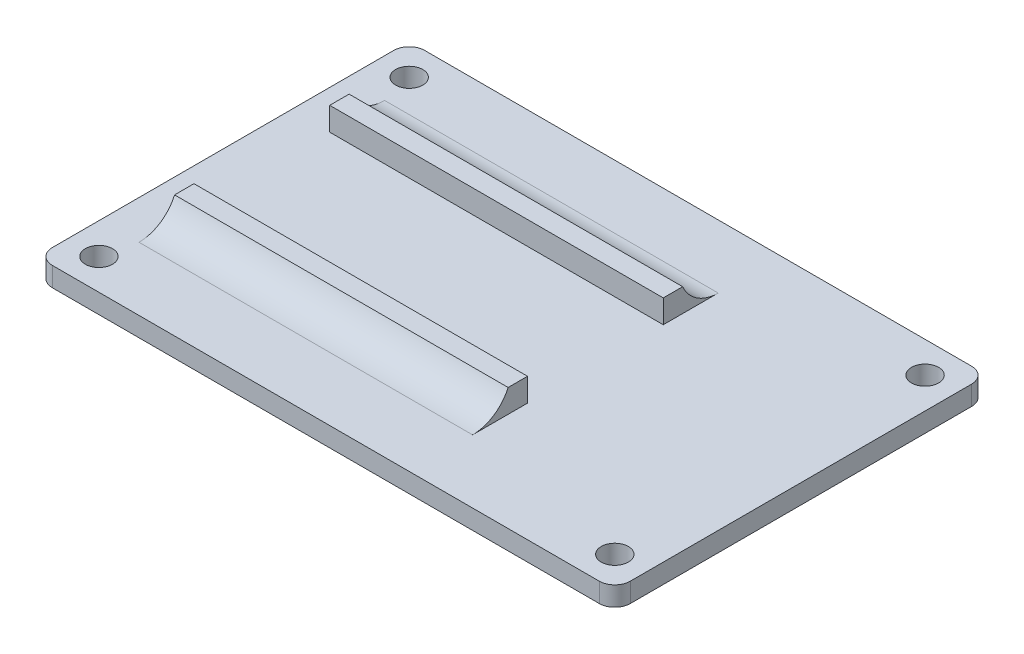
SolidWorks part; units mm, degrees
ref_plane "Front Plane" through (0, 0, 0) normal (0, 0, 1) x (1, 0, 0)
ref_plane "Top Plane" through (0, 0, 0) normal (0, 1, 0) x (1, 0, 0)
ref_plane "Right Plane" through (0, 0, 0) normal (1, 0, 0) x (0, 0, -1)
sketch "Sketch1" plane through (0, 0, 0) normal (0, 1, 0) x (1, 0, 0)
  line L2 (-52.4763, 21.334) -> (18.0237, 21.334)
  line L3 (20.0237, 19.334) -> (20.0237, -24.666)
  line L4 (18.0237, -26.666) -> (-52.4763, -26.666)
  line L5 (-54.4763, -24.666) -> (-54.4763, 19.334)
  circle A0 centre (-50.4763, 17.334) radius 1.75
  circle A1 centre (16.0237, 17.334) radius 1.75
  circle A2 centre (16.0237, -22.666) radius 1.75
  circle A3 centre (-50.4763, -22.666) radius 1.75
  arc A4 (-52.4763, -26.666) -> (-54.4763, -24.666) centre (-52.4763, -24.666) cw
  arc A5 (20.0237, -24.666) -> (18.0237, -26.666) centre (18.0237, -24.666) cw
  arc A6 (18.0237, 21.334) -> (20.0237, 19.334) centre (18.0237, 19.334) cw
  arc A7 (-54.4763, 19.334) -> (-52.4763, 21.334) centre (-52.4763, 19.334) cw
  dimension "D1" = 2
extrude "Boss-Extrude1" add sketch "Sketch1" along normal blind 2.5
sketch "Sketch2" plane through (0, 2.5, 0) normal (0, 1, 0) x (1, 0, 0)
  line L0 (-49.4763, 8.584) -> (-6.4763, 8.584)
  line L1 (-49.4763, 8.584) -> (-49.4763, 6.084)
  line L2 (-6.4763, -13.916) -> (-49.4763, -13.916)
  line L3 (-49.4763, 6.084) -> (-6.4763, 6.084)
  line L4 (-6.4763, -13.916) -> (-6.4763, -11.416)
  line L5 (-6.4763, -11.416) -> (-49.4763, -11.416)
  line L6 (-49.4763, -11.416) -> (-49.4763, -13.916)
  line L7 (-6.4763, 6.084) -> (-6.4763, 8.584)
  dimension "D1" = 2.5
extrude "Boss-Extrude2" add sketch "Sketch2" along normal blind 3
fillet "Fillet1" radius 5 2 edges at (-27.9763, 2.5, -8.584) (-27.9763, 2.5, 13.916)
